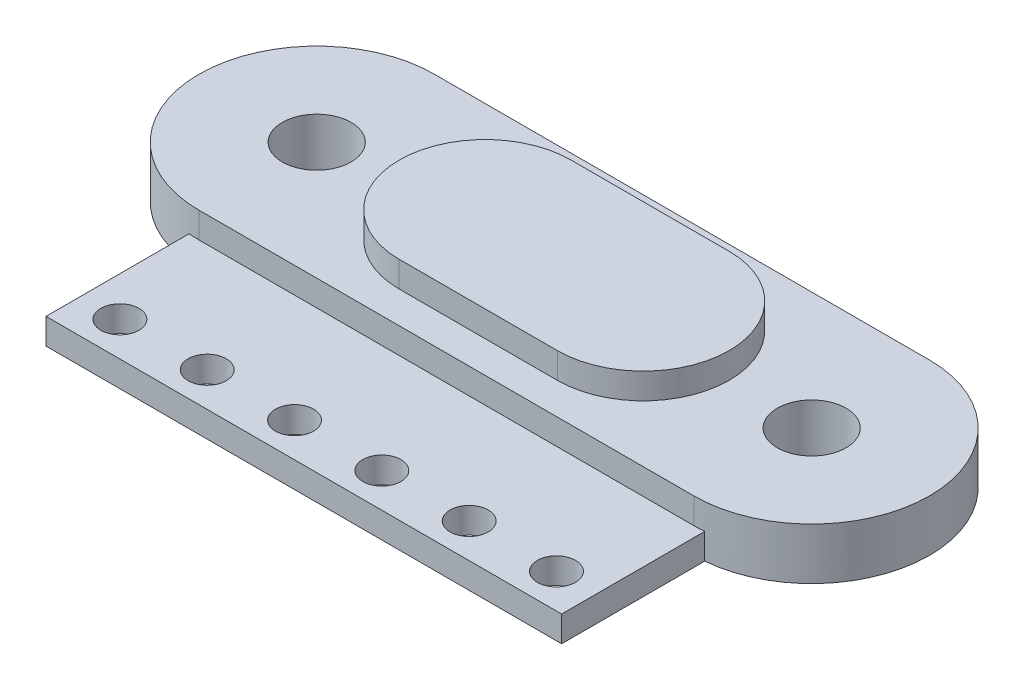
SolidWorks part; units mm, degrees
ref_plane "前视基准面" through (0, 0, 0) normal (0, 0, 1) x (1, 0, 0)
ref_plane "上视基准面" through (0, 0, 0) normal (0, 1, 0) x (1, 0, 0)
ref_plane "右视基准面" through (0, 0, 0) normal (1, 0, 0) x (0, 0, -1)
other "Configuration Table"
sketch "草图2" plane through (0, 0, 0) normal (0, 1, 0) x (1, 0, 0)
  line L0 (-14.4, 0) -> (0, 0) construction
  line L1 (-14.4, 3.425) -> (0, 3.425)
  line L2 (-14.4, -3.425) -> (0, -3.425)
  line L3 (-14.7, -3.4118) -> (-14.7, -7.575)
  line L4 (-14.7, -7.575) -> (0.3, -7.575)
  line L5 (-7.2, 0) -> (-7.2, -7.575) construction
  line L6 (0.3, -3.4118) -> (0.3, -7.575)
  arc A0 (-14.4, 3.425) -> (-14.4, -3.425) centre (-14.4, 0) ccw
  arc A1 (0, -3.425) -> (0, 3.425) centre (0, 0) ccw
  circle A2 centre (0, 0) radius 1
  circle A3 centre (-14.4, 0) radius 1
  circle A4 centre (-8.47, -6.575) radius 0.5544
  circle A5 centre (-11.01, -6.575) radius 0.5544
  circle A6 centre (-13.55, -6.575) radius 0.5544
  circle A7 centre (-5.93, -6.575) radius 0.5544
  circle A8 centre (-3.39, -6.575) radius 0.5544
  circle A9 centre (-0.85, -6.575) radius 0.5544
  point P3 (-7.2, 0)
  dimension "D5" = 2
  dimension "D6" = 2
  dimension "D1" = 6.85
  dimension "D2" = 14.4
  dimension "D3" = 15
  dimension "D4" = 11
  dimension "D7" = 1.27
  dimension "D8" = 1
  dimension "D9" = 3
extrude "凸台-拉伸3" add sketch "草图2" along normal blind 0.75 contours L2 A1 L1 A0 A3 A2 | A1 L2 A0 L3 L4 L6 A8 A4 A5 A6 A7 A9 region at (-7.2, 0, 0) region at (-7.2, 0, 5.3896)
extrude "凸台-拉伸4" add sketch "草图2<5>" along normal blind 1.5 contours A3 | A2 | L1 A1 L2 A0 region at (0, 0, 0) region at (-14.4, 0, 0)
sketch "草图2<5>" plane through (0, 0, 0) normal (0, 1, 0) x (1, 0, 0) same geometry as "草图2"
sketch "草图3" plane through (0, 1.5, 0) normal (0, 1, 0) x (1, 0, 0)
  line L0 (-9.5, 0) -> (-4.9, 0) construction
  line L1 (-14.4, 0) -> (0, 0) construction
  line L2 (-9.5, 2.5) -> (-4.9, 2.5)
  line L3 (-9.5, -2.5) -> (-4.9, -2.5)
  arc A0 (-9.5, 2.5) -> (-9.5, -2.5) centre (-9.5, 0) ccw
  arc A1 (-4.9, -2.5) -> (-4.9, 2.5) centre (-4.9, 0) ccw
  point P5 (-7.2, 0)
  point P10 (-12, 0)
  point P11 (-2.4, 0)
  dimension "D1" = 5
  dimension "D2" = 9.6
extrude "凸台-拉伸5" add sketch "草图3" along normal blind 0.75
